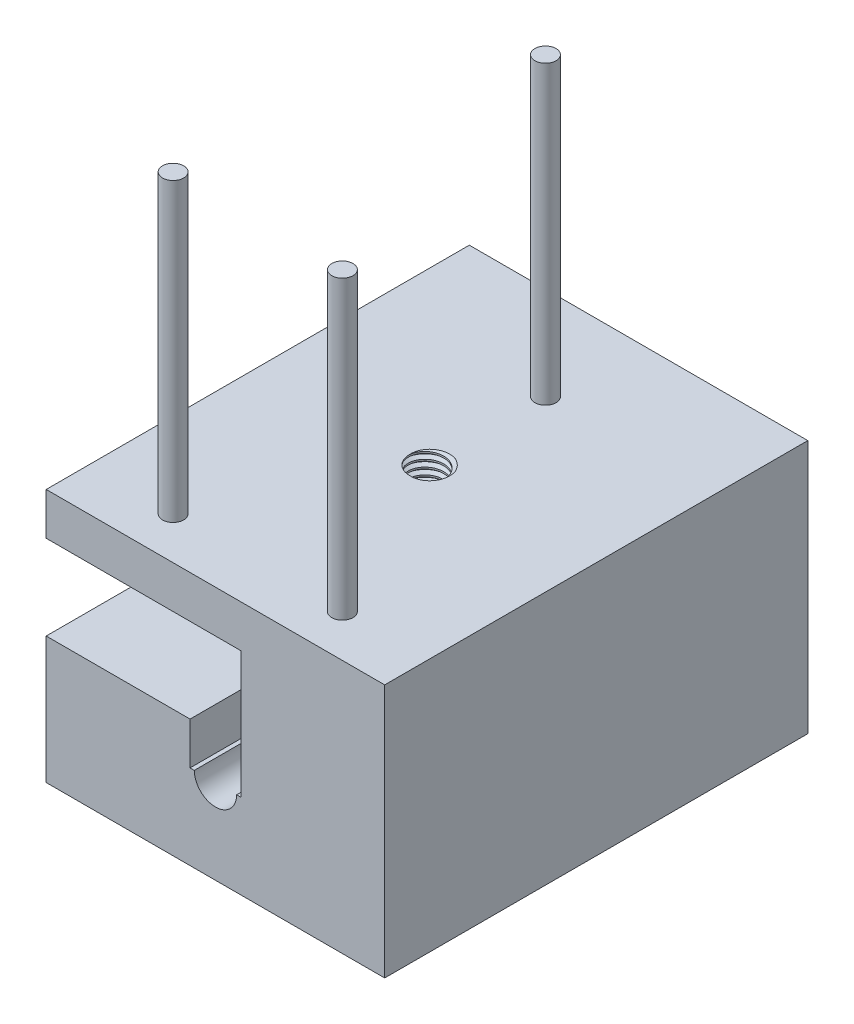
SolidWorks part; units mm, degrees
ref_plane "Front Plane" through (0, 0, 0) normal (0, 0, 1) x (1, 0, 0)
ref_plane "Top Plane" through (0, 0, 0) normal (0, 1, 0) x (1, 0, 0)
ref_plane "Right Plane" through (0, 0, 0) normal (1, 0, 0) x (0, 0, -1)
sketch "Sketch1" plane through (0, 0, 0) normal (0, 0, 1) x (1, 0, 0)
  line L0 (0, 0) -> (0, 30)
  line L1 (0, 30) -> (-40, 30)
  line L2 (-40, 30) -> (-40, 25)
  line L3 (-40, 25) -> (-17, 25)
  line L4 (-17, 25) -> (-17, 10)
  line L7 (-23, 10) -> (-23, 15)
  line L8 (-23, 15) -> (-40, 15)
  line L9 (-40, 15) -> (-40, 0)
  line L10 (-40, 0) -> (0, 0)
  line L11 (-17, 10) -> (-23, 10) construction
  line L12 (-23, 10) -> (-22.5, 10)
  line L13 (-17, 10) -> (-17.5, 10)
  arc A1 (-22.5, 10) -> (-17.5, 10) centre (-20, 10) ccw
  dimension "D7" = 5
  dimension "D1" = 30
  dimension "D2" = 40
  dimension "D3" = 5
  dimension "D4" = 15
  dimension "D5" = 17
  dimension "D6" = 17
  dimension "D8" = 5
extrude "Boss-Extrude1" add sketch "Sketch1" along normal blind 50
sketch "Sketch2" plane through (0, 30, 0) normal (0, 1, 0) x (1, 0, 0)
  line L0 (-20, -50) -> (-20, 0) construction
  line L1 (0, -50) -> (-40, -50) construction
  line L2 (0, 0) -> (-40, 0) construction
  point P6 (-20, -25)
hole_wizard "Tap Drill for M5x0.8 Tap1" positions "Sketch3" profile "Sketch4" hole size "M5x0.8" standard "ANSI Metric"
sketch "Sketch3" plane through (0, 30, 0) normal (0, 1, 0) x (1, 0, 0)
  point P0 (-20, -25)
sketch "Sketch4" plane through (-20, 30, 25) normal (1, 0, 0) x (0, 0, 1)
  line L0 (0, 0) -> (0, 6.2608)
  line L1 (0, 6.2608) -> (2.1, 4.999)
  line L2 (2.1, 4.999) -> (2.1, 0)
  line L5 (2.1, 0) -> (0, 0)
  line L10 (0, 6.2608) -> (-2.1, 4.999) construction
  line L11 (0, -6.35) -> (0, 107.95) construction
  dimension "Hole Dia." = 4.2
  dimension "Hole Depth" = 4.999
  dimension "Drill Angle" = 118
thread "Thread1" pitch 0.8 method cut profile "Thread Profile1" start angle 0, offset 3, length 10, pitch 0.8, diameter 4.2
ref_plane "Plane1" through (-22.1, 33, 25) normal (0, 0, 1) x (-1, 0, 0)
sketch "Thread Profile1" plane through (-22.1, 33, 25) normal (0, 0, 1) x (-1, 0, 0)
  line L0 (0, 0) -> (0, 0.8) construction
  line L1 (0, 0) -> (0.433, 0.25)
  line L2 (0.433, 0.25) -> (0.433, 0.35)
  line L3 (0.433, 0.35) -> (0, 0.6)
  line L4 (0.433, 0.3) -> (0, 0.3) construction
  line L11 (0, 0) -> (0, 0.6)
  point P2 (0, 0)
  dimension "Pitch" = 0.8
  dimension "Profile_Angle" = 60
  dimension "Profile_Land" = 0.1
  dimension "Profile_Height" = 0.433
sketch "Sketch7" plane through (0, 30, 0) normal (0, 1, 0) x (1, 0, 0)
  line L0 (-20, -50) -> (-20, 0) construction
  circle A0 centre (-20, -11) radius 1.25
  dimension "D2" = 2.5
  dimension "D1" = 14
extrude "Boss-Extrude2" add sketch "Sketch7" along normal blind 35
sketch "Sketch8" plane through (0, 30, 0) normal (0, 1, 0) x (1, 0, 0)
  line L0 (-20, -50) -> (-20, 0) construction
  line L3 (-20, -50) -> (-20, 0) construction
  circle A0 centre (-30, -45) radius 1.25
  circle A1 centre (-20, -11) radius 1.25 construction
  circle A2 centre (-10, -45) radius 1.25
  dimension "D1" = 10
  dimension "D2" = 20
extrude "Boss-Extrude3" add sketch "Sketch8" along normal blind 35
